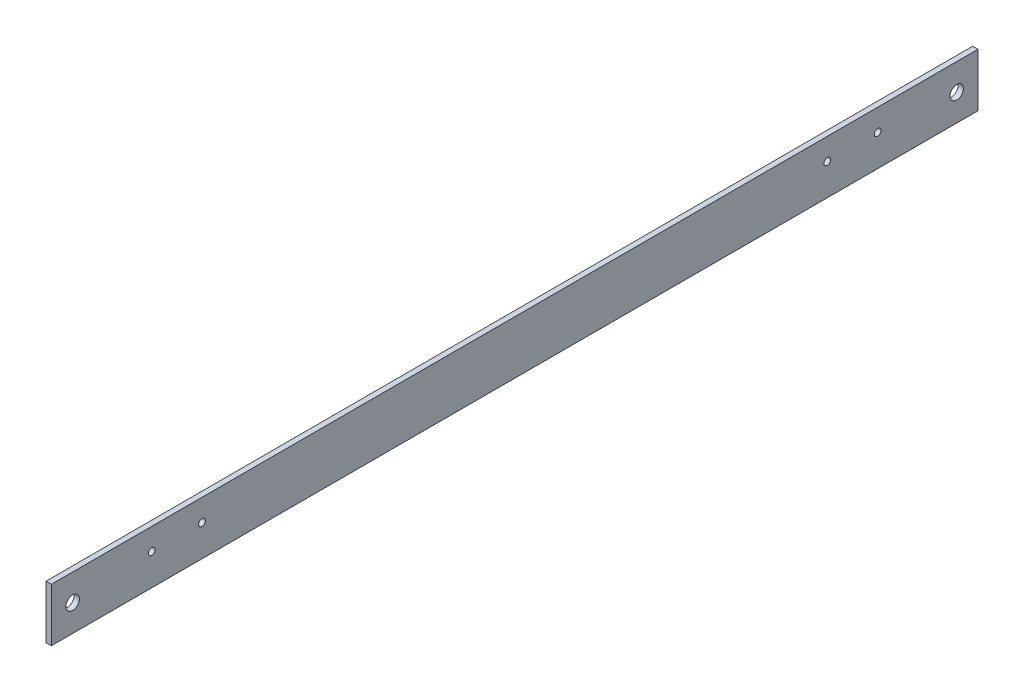
SolidWorks part; units mm, degrees
ref_plane "Front Plane" through (0, 0, 0) normal (0, 0, 1) x (1, 0, 0)
ref_plane "Top Plane" through (0, 0, 0) normal (0, 1, 0) x (1, 0, 0)
ref_plane "Right Plane" through (0, 0, 0) normal (1, 0, 0) x (0, 0, -1)
sketch "Sketch1" plane through (0, 0, 0) normal (1, 0, 0) x (0, 0, -1)
  line L1 (0, 0) -> (552.45, 0)
  line L2 (0, 0) -> (0, 31.75)
  line L3 (0, 31.75) -> (552.45, 31.75)
  line L4 (552.45, 0) -> (552.45, 31.75)
  circle A0 centre (12.7, 15.875) radius 4
  circle A1 centre (539.75, 15.875) radius 4
  circle A2 centre (462.625, 18.75) radius 2
  circle A3 centre (492.625, 18.75) radius 2
  circle A4 centre (59.825, 18.75) radius 2
  circle A5 centre (89.825, 18.75) radius 2
  dimension "D3" = 8
  dimension "D7" = 4
  dimension "D1" = 31.75
  dimension "D2" = 552.45
  dimension "D4" = 15.875
  dimension "D5" = 12.7
  dimension "D6" = 12.7
  dimension "D8" = 30
  dimension "D10" = 13
  dimension "D9" = 59.825
  dimension "D11" = 462.625
  dimension "D12" = 492.625
  dimension "D13" = 59.825
  dimension "D14" = 30
extrude "Boss-Extrude2" add sketch "Sketch1" along normal blind 3.175
equation "\"RailThickness\"= .125in'Spec"
equation "\"VSWidth\"= 1.25in'Spec"
equation "\"SideRailLength\"= 21.75in"
equation "\"StepperHolePadSize\"= \"StepperHoleDiameter\""
equation "\"D1@Sketch1\"=\"TopRailHeight\""
equation "\"D2@Sketch1\"=\"SideRailLength\""
equation "\"FrameFastenerHoleDiameter\"= 8mm"
equation "\"D3@Sketch1\"=\"FrameFastenerHoleDiameter\""
equation "\"D4@Sketch1\"=\"TopRailHeight\"/2"
equation "\"D5@Sketch1\"=\"FrameFastenerHoleOffsetFromEdge\""
equation "\"D6@Sketch1\"=\"FrameFastenerHoleOffsetFromEdge\""
equation "\"D1@Boss-Extrude2\"=\"RailThickness\""
equation "\"FrameFastenerHoleOffsetFromEdge\" = \"VSWidth\" / 2 - \"GapBetweenVerticalSupportsAndRails\" / 2"
equation "\"TopRailHeight\"= 1.25in"
equation "\"GapBetweenVerticalSupportsAndRails\"= \"RailThickness\" * 2"
equation "\"AngleBracketSmallHoleDiameter\"= 4mm"
equation "\"AngleBracketSlotDistanceBetweenHoles\"= 30mm"
equation "\"AngleBracketSlotDistanceFromTop\"= 13mm"
equation "\"AngleBracketSlotDistanceFromCorner\" = \"AngleBracketSlotDistanceFromBack\" - \"GapBetweenVerticalSupportsAndRails\" / 2'Equals 61.825"
equation "\"D7@Sketch1\"=\"AngleBracketSmallHoleDiameter\""
equation "\"D8@Sketch1\"=\"AngleBracketSlotDistanceBetweenHoles\""
equation "\"D10@Sketch1\"=\"AngleBracketSlotDistanceFromTop\""
equation "\"D9@Sketch1\"= \"AngleBracketSlotDistanceFromCorner\" - 2mm 'Minus 2mm to get screw hole in middle of slot"
equation "\"AngleBracketSlotDistanceFromBack\"= 65mm"
equation "\"D13@Sketch1\"= \"AngleBracketSlotDistanceFromCorner\" - 2mm'Minus 2mm to get screw hole in middle of slot"
equation "\"D14@Sketch1\"=\"AngleBracketSlotDistanceBetweenHoles\""
